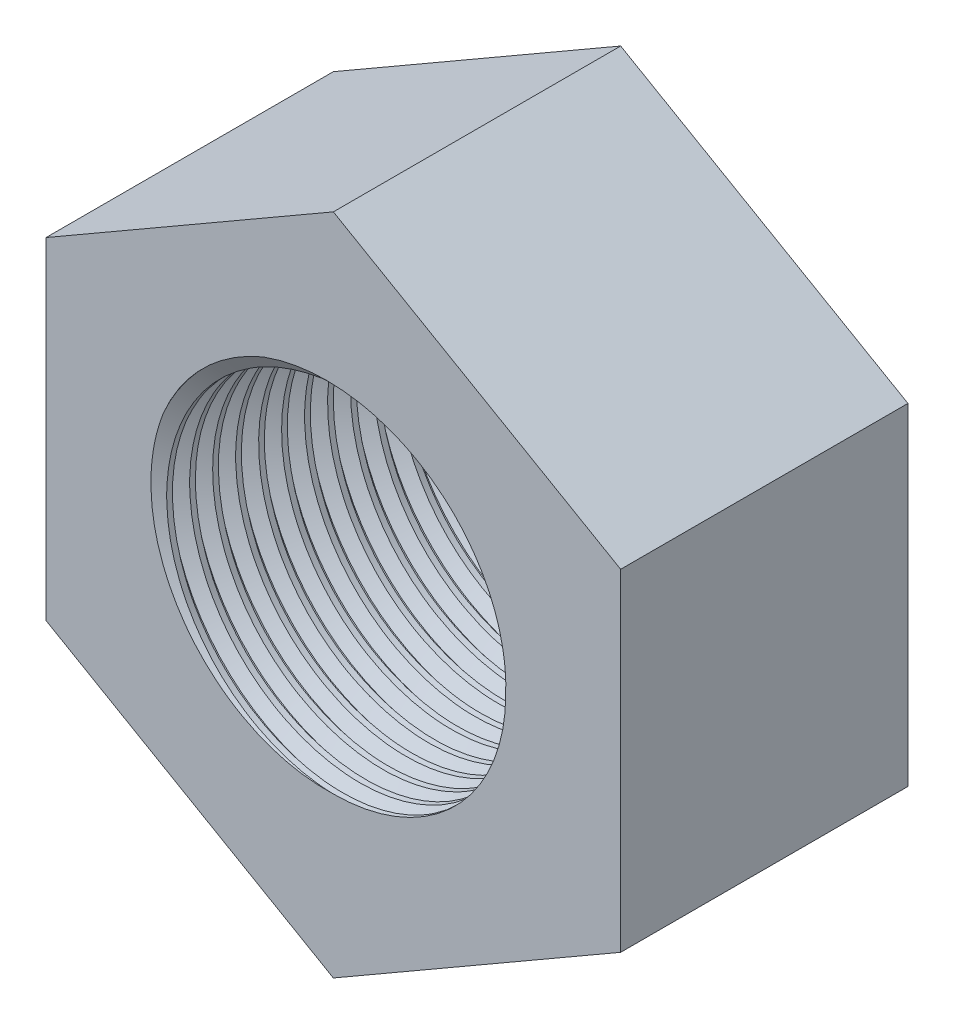
SolidWorks part; units mm, degrees
material "Cobre"
ref_plane "Front" through (0, 0, 0) normal (0, 0, 1) x (1, 0, 0)
ref_plane "Top" through (0, 0, 0) normal (0, 1, 0) x (1, 0, 0)
ref_plane "Right" through (0, 0, 0) normal (1, 0, 0) x (0, 0, -1)
sketch "Croquis1" plane through (0, 0, 0) normal (0, 0, 1) x (1, 0, 0)
  line L1 (0, 5.7735) -> (-5, 2.8868)
  line L2 (-5, 2.8868) -> (-5, -2.8868)
  line L3 (-5, -2.8868) -> (0, -5.7735)
  line L4 (0, -5.7735) -> (5, -2.8868)
  line L5 (5, -2.8868) -> (5, 2.8868)
  line L6 (5, 2.8868) -> (0, 5.7735)
  circle A0 centre (0, 0) radius 5 construction
  circle A1 centre (0, 0) radius 3
  dimension "D1" = 10
  dimension "D2" = 6
extrude "Saliente-Extruir1" add sketch "Croquis1" along normal blind 5
thread "Rosca1" pitch 0.4 method cut profile "Perfil de rosca1" start angle 0, offset 1, length 15, pitch 0.4, diameter 6
ref_plane "Plano1" through (-3, 0, 6) normal (0, -1, 0) x (-1, 0, 0)
sketch "Perfil de rosca1" plane through (-3, 0, 6) normal (0, -1, 0) x (-1, 0, 0)
  line L0 (0, 0) -> (0, 0.4) construction
  line L1 (0, 0) -> (0.2165, 0.125)
  line L2 (0.2165, 0.125) -> (0.2165, 0.175)
  line L3 (0.2165, 0.175) -> (0, 0.3)
  line L4 (0.2165, 0.15) -> (0, 0.15) construction
  line L11 (0, 0) -> (0, 0.3)
  point P2 (0, 0)
  dimension "Pitch" = 0.4
  dimension "Profile_Angle" = 60
  dimension "Profile_Land" = 0.05
  dimension "Profile_Height" = 0.2165
